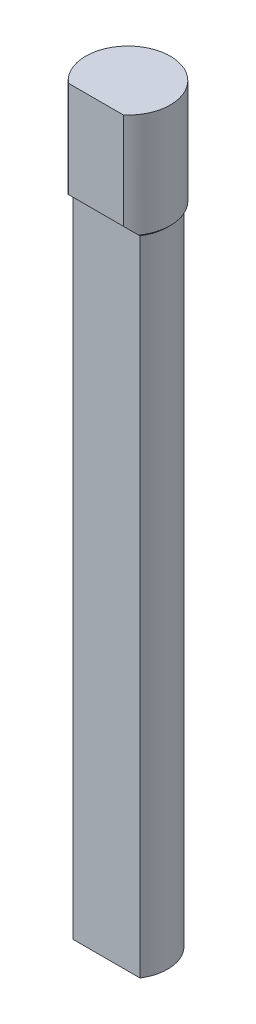
SolidWorks part; units mm, degrees
ref_plane "Front Plane" through (0, 0, 0) normal (0, 0, 1) x (1, 0, 0)
ref_plane "Top Plane" through (0, 0, 0) normal (0, 1, 0) x (1, 0, 0)
ref_plane "Right Plane" through (0, 0, 0) normal (1, 0, 0) x (0, 0, -1)
sketch "Sketch1" plane through (0, 0, 0) normal (0, 1, 0) x (1, 0, 0)
  line L3 (-3.1129, -2) -> (3.1129, -2)
  arc A1 (3.1129, -2) -> (-3.1129, -2) centre (0, 0) ccw
  dimension "D1" = 7.4
extrude "Boss-Extrude1" add sketch "Sketch1" along normal blind 60
ref_plane "Plane1" through (0, 0, -3.7) normal (0, 0, -1) x (-1, 0, 0)
sketch "Sketch2" plane through (0, 0, -3.7) normal (0, 0, -1) x (-1, 0, 0)
  line L0 (-3.75, 0) -> (3.75, 0) construction
  line L1 (0.75, 49.5) -> (-0.75, 49.5)
  line L2 (0.75, 49.5) -> (0.75, 46)
  line L3 (0.75, 46) -> (-0.75, 46)
  line L4 (-0.75, 49.5) -> (-0.75, 46)
  point P7 (0, 46)
  point P9 (0, 0)
  point P10 (0, 0)
  dimension "D1" = 3.5
  dimension "D2" = 1.5
  dimension "D3" = 0
  dimension "D4" = 46
extrude "Boss-Extrude2" add sketch "Sketch2" along normal blind 0.7 separate body
extrude "Boss-Extrude3" add sketch "Sketch2<2>" against normal blind 0.25
sketch "Sketch2<2>" plane through (0, 0, -3.7) normal (0, 0, -1) x (-1, 0, 0) same geometry as "Sketch2"
chamfer "Chamfer1" distance 0.6 angle 45 1 edges at (0, 49.5, -4.4)
chamfer "Chamfer2" distance 0.6 angle 45 1 edges at (0, 46, -4.4)
ref_plane "Plane2" through (0, 60, 0) normal (0, 1, 0) x (1, 0, 0)
sketch "Sketch3" plane through (0, 60, 0) normal (0, 1, 0) x (1, 0, 0)
  line L3 (-2.5695, -3) -> (2.5695, -3)
  arc A1 (2.5695, -3) -> (-2.5695, -3) centre (0, 0) ccw
  dimension "D1" = 7.9
extrude "Boss-Extrude4" add sketch "Sketch3" along normal blind 10
chamfer "Chamfer3" distance 1 angle 45 1 edges at (0, 60, 3)
chamfer "Chamfer4" distance 0.25 angle 45 1 edges at (0, 60, -3.95)
